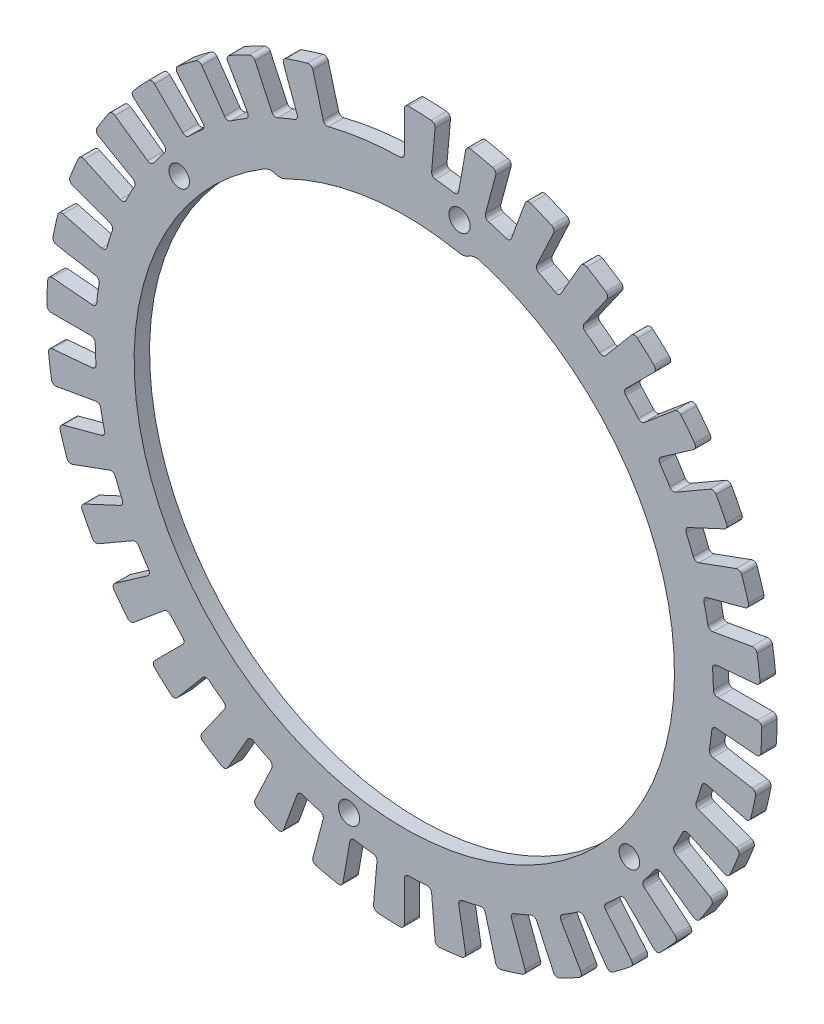
SolidWorks part; units mm, degrees
ref_plane "Front Plane" through (0, 0, 0) normal (0, 0, 1) x (1, 0, 0)
ref_plane "Top Plane" through (0, 0, 0) normal (0, 1, 0) x (1, 0, 0)
ref_plane "Right Plane" through (0, 0, 0) normal (1, 0, 0) x (0, 0, -1)
sketch "Sketch1" plane through (0, 0, 0) normal (0, 0, 1) x (1, 0, 0)
  line L0 (0, 82.7) -> (0, 71.5) construction
  line L1 (7.2078, 82.3853) -> (6.2316, 71.2279) construction
  line L2 (0, 71.5) -> (0, 0) construction
  line L3 (6.2316, 71.2279) -> (0, 0) construction
  line L4 (12.5883, 71.3918) -> (14.186, 80.4528) construction
  line L5 (12.5883, 71.3918) -> (0, 0) construction
  line L8 (0, 0) -> (12.7842, 65.769) construction
  line L12 (13.6428, 70.1863) -> (12.7842, 65.769) construction
  line L15 (12.7842, 65.769) -> (11.9256, 61.3517) construction
  line L18 (7.3144, 72.1301) -> (6.3182, 72.2172) construction
  line L21 (7.3144, 72.1301) -> (7.2135, 71.1352) construction
  line L24 (12.5883, 71.3918) -> (11.6035, 71.5654) construction
  line L27 (11.6035, 71.5654) -> (11.4434, 70.5783) construction
  line L30 (1.0122, 82.6938) -> (1, 81.6939) construction
  line L33 (1, 81.6939) -> (0, 81.6939) construction
  line L36 (7.1201, 81.383) -> (6.1239, 81.4702) construction
  line L39 (6.1239, 81.4702) -> (6.1989, 82.4674) construction
  line L42 (7.1201, 81.383) -> (6.3182, 72.2172)
  line L45 (0, 81.6939) -> (0, 72.4931)
  line L48 (0, 72.4931) -> (-1, 72.4931) construction
  line L51 (-1, 72.4931) -> (-0.9862, 71.4932) construction
  line L109 (0, -82.7) -> (0, -71.5) [skipped]
  line L111 (14.3607, 81.4436) -> (12.4158, 70.4138) [skipped]
  line L115 (41.35, 71.6203) -> (35.75, 61.9208) [skipped]
  line L117 (53.1585, 63.3519) -> (45.9593, 54.7722) [skipped]
  line L118 (-63.3519, -53.1585) -> (-54.7722, -45.9593) [skipped]
  line L119 (63.3519, 53.1585) -> (54.7722, 45.9593) [skipped]
  line L121 (71.6203, 41.35) -> (61.9208, 35.75) [skipped]
  line L123 (77.7126, 28.2851) -> (67.188, 24.4544) [skipped]
  line L125 (81.4436, 14.3607) -> (70.4138, 12.4158) [skipped]
  line L127 (82.7, 0) -> (71.5, 0) [skipped]
  line L129 (81.4436, -14.3607) -> (70.4138, -12.4158) [skipped]
  line L131 (77.7126, -28.2851) -> (67.188, -24.4544) [skipped]
  line L133 (71.6203, -41.35) -> (61.9208, -35.75) [skipped]
  line L135 (63.3519, -53.1585) -> (54.7722, -45.9593) [skipped]
  line L137 (53.1585, -63.3519) -> (45.9593, -54.7722) [skipped]
  line L139 (41.35, -71.6203) -> (35.75, -61.9208) [skipped]
  line L141 (28.2851, -77.7126) -> (24.4544, -67.188) [skipped]
  line L142 (14.3607, -81.4436) -> (12.4158, -70.4138) [skipped]
  line L143 (34.9505, 74.9517) -> (30.2172, 64.801) [skipped]
  line L144 (47.4348, 67.7439) -> (41.0107, 58.5694) [skipped]
  line L145 (58.4777, 58.4777) -> (50.5581, 50.5581) [skipped]
  line L146 (67.7439, 47.4348) -> (58.5694, 41.0107) [skipped]
  line L147 (74.9517, 34.9505) -> (64.801, 30.2172) [skipped]
  line L148 (79.8821, 21.4043) -> (69.0637, 18.5056) [skipped]
  line L149 (82.3853, 7.2078) -> (71.2279, 6.2316) [skipped]
  line L150 (82.3853, -7.2078) -> (71.2279, -6.2316) [skipped]
  line L151 (79.8821, -21.4043) -> (69.0637, -18.5056) [skipped]
  line L152 (74.9517, -34.9505) -> (64.801, -30.2172) [skipped]
  line L153 (67.7439, -47.4348) -> (58.5694, -41.0107) [skipped]
  line L154 (58.4777, -58.4777) -> (50.5581, -50.5581) [skipped]
  line L155 (47.4348, -67.7439) -> (41.0107, -58.5694) [skipped]
  line L156 (34.9505, -74.9517) -> (30.2172, -64.801) [skipped]
  line L157 (21.4043, -79.8821) -> (18.5056, -69.0637) [skipped]
  line L158 (7.2078, -82.3853) -> (6.2316, -71.2279) [skipped]
  line L159 (-7.2078, -82.3853) -> (-6.2316, -71.2279) [skipped]
  line L160 (-21.4043, -79.8821) -> (-18.5056, -69.0637) [skipped]
  line L161 (-34.9505, -74.9517) -> (-30.2172, -64.801) [skipped]
  line L162 (-47.4348, -67.7439) -> (-41.0107, -58.5694) [skipped]
  line L163 (-58.4777, -58.4777) -> (-50.5581, -50.5581) [skipped]
  line L164 (-67.7439, -47.4348) -> (-58.5694, -41.0107) [skipped]
  line L165 (-74.9517, -34.9505) -> (-64.801, -30.2172) [skipped]
  line L166 (-79.8821, -21.4043) -> (-69.0637, -18.5056) [skipped]
  line L167 (-82.3853, -7.2078) -> (-71.2279, -6.2316) [skipped]
  line L168 (-82.3853, 7.2078) -> (-71.2279, 6.2316) [skipped]
  line L169 (-79.8821, 21.4043) -> (-69.0637, 18.5056) [skipped]
  line L170 (-74.9517, 34.9505) -> (-64.801, 30.2172) [skipped]
  line L171 (-67.7439, 47.4348) -> (-58.5694, 41.0107) [skipped]
  line L172 (-58.4777, 58.4777) -> (-50.5581, 50.5581) [skipped]
  line L173 (-47.4348, 67.7439) -> (-41.0107, 58.5694) [skipped]
  line L174 (-34.9505, 74.9517) -> (-30.2172, 64.801) [skipped]
  line L175 (-21.4043, 79.8821) -> (-18.5056, 69.0637) [skipped]
  line L176 (21.4043, 79.8821) -> (18.5056, 69.0637) [skipped]
  line L209 (0, 0) -> (-12.7842, -65.769) construction
  line L210 (0, 0) -> (-52.0688, 42.1645) construction
  line L211 (0, 0) -> (52.0688, -42.1645) construction
  line L212 (14.186, 80.4528) -> (12.5883, 71.3918)
  line L213 (21.1439, 78.9102) -> (18.7626, 70.023)
  line L214 (27.941, 76.7671) -> (24.7941, 68.1212)
  line L215 (34.5253, 74.0398) -> (30.6369, 65.7011)
  line L216 (40.8469, 70.749) -> (36.2466, 62.7809)
  line L217 (46.8577, 66.9197) -> (41.5803, 59.3829)
  line L218 (52.5118, 62.5811) -> (46.5977, 55.5329)
  line L219 (57.7663, 57.7663) -> (51.2604, 51.2604)
  line L220 (62.5811, 52.5118) -> (55.5329, 46.5977)
  line L221 (66.9197, 46.8577) -> (59.3829, 41.5803)
  line L222 (70.749, 40.8469) -> (62.7809, 36.2466)
  line L223 (74.0398, 34.5253) -> (65.7011, 30.6369)
  line L224 (76.7671, 27.941) -> (68.1212, 24.7941)
  line L225 (78.9102, 21.1439) -> (70.023, 18.7626)
  line L226 (80.4528, 14.186) -> (71.3918, 12.5883)
  line L227 (81.383, 7.1201) -> (72.2172, 6.3182)
  line L228 (81.6939, 0) -> (72.4931, 0)
  line L229 (81.383, -7.1201) -> (72.2172, -6.3182)
  line L230 (80.4528, -14.186) -> (71.3918, -12.5883)
  line L231 (78.9102, -21.1439) -> (70.023, -18.7626)
  line L232 (76.7671, -27.941) -> (68.1212, -24.7941)
  line L233 (74.0398, -34.5253) -> (65.7011, -30.6369)
  line L234 (70.749, -40.8469) -> (62.7809, -36.2466)
  line L235 (66.9197, -46.8577) -> (59.3829, -41.5803)
  line L236 (62.5811, -52.5118) -> (55.5329, -46.5977)
  line L237 (57.7663, -57.7663) -> (51.2604, -51.2604)
  line L238 (52.5118, -62.5811) -> (46.5977, -55.5329)
  line L239 (46.8577, -66.9197) -> (41.5803, -59.3829)
  line L240 (40.8469, -70.749) -> (36.2466, -62.7809)
  line L241 (34.5253, -74.0398) -> (30.6369, -65.7011)
  line L242 (27.941, -76.7671) -> (24.7941, -68.1212)
  line L243 (21.1439, -78.9102) -> (18.7626, -70.023)
  line L244 (14.186, -80.4528) -> (12.5883, -71.3918)
  line L245 (7.1201, -81.383) -> (6.3182, -72.2172)
  line L246 (0, -81.6939) -> (0, -72.4931)
  line L247 (-7.1201, -81.383) -> (-6.3182, -72.2172)
  line L248 (-14.186, -80.4528) -> (-12.5883, -71.3918)
  line L249 (-21.1439, -78.9102) -> (-18.7626, -70.023)
  line L250 (-27.941, -76.7671) -> (-24.7941, -68.1212)
  line L251 (-34.5253, -74.0398) -> (-30.6369, -65.7011)
  line L252 (-40.8469, -70.749) -> (-36.2466, -62.7809)
  line L253 (-46.8577, -66.9197) -> (-41.5803, -59.3829)
  line L254 (-52.5118, -62.5811) -> (-46.5977, -55.5329)
  line L255 (-57.7663, -57.7663) -> (-51.2604, -51.2604)
  line L256 (-62.5811, -52.5118) -> (-55.5329, -46.5977)
  line L257 (-66.9197, -46.8577) -> (-59.3829, -41.5803)
  line L258 (-70.749, -40.8469) -> (-62.7809, -36.2466)
  line L259 (-74.0398, -34.5253) -> (-65.7011, -30.6369)
  line L260 (-76.7671, -27.941) -> (-68.1212, -24.7941)
  line L261 (-78.9102, -21.1439) -> (-70.023, -18.7626)
  line L262 (-80.4528, -14.186) -> (-71.3918, -12.5883)
  line L263 (-81.383, -7.1201) -> (-72.2172, -6.3182)
  line L264 (-81.6939, 0) -> (-72.4931, 0)
  line L265 (-81.383, 7.1201) -> (-72.2172, 6.3182)
  line L266 (-80.4528, 14.186) -> (-71.3918, 12.5883)
  line L267 (-78.9102, 21.1439) -> (-70.023, 18.7626)
  line L268 (-76.7671, 27.941) -> (-68.1212, 24.7941)
  line L269 (-74.0398, 34.5253) -> (-65.7011, 30.6369)
  line L270 (-70.749, 40.8469) -> (-62.7809, 36.2466)
  line L271 (-66.9197, 46.8577) -> (-59.3829, 41.5803)
  line L272 (-62.5811, 52.5118) -> (-55.5329, 46.5977)
  line L273 (-57.7663, 57.7663) -> (-51.2604, 51.2604)
  line L274 (-52.5118, 62.5811) -> (-46.5977, 55.5329)
  line L275 (-46.8577, 66.9197) -> (-41.5803, 59.3829)
  line L276 (-40.8469, 70.749) -> (-36.2466, 62.7809)
  line L277 (-34.5253, 74.0398) -> (-30.6369, 65.7011)
  line L278 (-27.941, 76.7671) -> (-24.7941, 68.1212)
  line L279 (-21.1439, 78.9102) -> (-18.7626, 70.023)
  line L280 (-0.9864, 71.4932) -> (-0.9862, 71.4932)
  line L281 (-32.3995, 53.4464) -> (-30.8444, 50.881) construction
  line L282 (-30.8444, 50.881) -> (-29.8635, 53.7161) construction
  line L283 (-29.8635, 53.7161) -> (-28.8826, 56.5512) construction
  line L284 (-28.8826, 56.5512) -> (-27.5181, 53.8795) construction
  line L285 (17.4626, 60.0109) -> (16.6244, 57.1304) construction
  line L286 (16.6244, 57.1304) -> (14.9432, 59.615) construction
  line L289 (13.262, 62.0997) -> (14.9432, 59.615) construction
  line L290 (-7.4414, 56.5227) -> (0, 0) construction
  line L291 (-27.5181, 53.8795) -> (-7.4414, 56.5227) construction
  line L292 (-7.4414, 56.5227) -> (12.6354, 59.1658) construction
  line L293 (13.262, 62.0997) -> (12.6354, 59.1658) construction
  line L294 (-28.4278, 55.6607) -> (13.0531, 61.1217) construction
  circle A0 centre (0, 0) radius 82.7 construction
  arc A1 (-32.3995, 53.4464) -> (17.4626, 60.0109) centre (0, 0) ccw
  circle A73 centre (12.7842, 65.769) radius 2.4585
  circle A74 centre (12.7842, 65.769) radius 2.987 construction
  arc A78 (0, 71.5) -> (6.2316, 71.2279) centre (0, 0) cw construction
  arc A79 (6.3182, 72.2172) -> (7.2135, 71.1352) centre (7.3144, 72.1301) ccw
  arc A80 (11.4434, 70.5783) -> (12.5883, 71.3918) centre (11.6035, 71.5654) ccw construction
  arc A81 (7.1201, 81.383) -> (6.1989, 82.4674) centre (6.1239, 81.4702) ccw
  arc A82 (0, 81.6939) -> (1.0122, 82.6938) centre (1, 81.6939) cw
  arc A83 (6.5367, 74.7146) -> (13.0236, 73.8606) centre (0, 0) cw [skipped]
  arc A84 (7.2135, 71.1352) -> (11.4434, 70.5783) centre (0, 0) cw
  arc A85 (0, 82.7) -> (7.2078, 82.3853) centre (0, 0) cw [skipped]
  arc A86 (1.0122, 82.6938) -> (6.1989, 82.4674) centre (0, 0) cw
  arc A87 (28.2851, 77.7126) -> (34.9505, 74.9517) centre (0, 0) cw [skipped]
  arc A88 (31.6964, 67.9731) -> (37.5, 64.9519) centre (0, 0) cw [skipped]
  arc A89 (41.35, 71.6203) -> (47.4348, 67.7439) centre (0, 0) cw [skipped]
  arc A90 (43.0182, 61.4364) -> (48.2091, 57.4533) centre (0, 0) cw [skipped]
  arc A91 (53.1585, 63.3519) -> (58.4777, 58.4777) centre (0, 0) cw [skipped]
  arc A92 (53.033, 53.033) -> (57.4533, 48.2091) centre (0, 0) cw [skipped]
  arc A93 (63.3519, 53.1585) -> (67.7439, 47.4348) centre (0, 0) cw [skipped]
  arc A94 (61.4364, 43.0182) -> (64.9519, 37.5) centre (0, 0) cw [skipped]
  arc A95 (71.6203, 41.35) -> (74.9517, 34.9505) centre (0, 0) cw [skipped]
  arc A96 (67.9731, 31.6964) -> (70.4769, 25.6515) centre (0, 0) cw [skipped]
  arc A97 (77.7126, 28.2851) -> (79.8821, 21.4043) centre (0, 0) cw [skipped]
  arc A98 (72.4444, 19.4114) -> (73.8606, 13.0236) centre (0, 0) cw [skipped]
  arc A99 (81.4436, 14.3607) -> (82.3853, 7.2078) centre (0, 0) cw [skipped]
  arc A100 (74.7146, 6.5367) -> (75, 0) centre (0, 0) cw [skipped]
  arc A101 (82.7, 0) -> (82.3853, -7.2078) centre (0, 0) cw [skipped]
  arc A102 (74.7146, -6.5367) -> (73.8606, -13.0236) centre (0, 0) cw [skipped]
  arc A103 (81.4436, -14.3607) -> (79.8821, -21.4043) centre (0, 0) cw [skipped]
  arc A104 (72.4444, -19.4114) -> (70.4769, -25.6515) centre (0, 0) cw [skipped]
  arc A105 (77.7126, -28.2851) -> (74.9517, -34.9505) centre (0, 0) cw [skipped]
  arc A106 (67.9731, -31.6964) -> (64.9519, -37.5) centre (0, 0) cw [skipped]
  arc A107 (71.6203, -41.35) -> (67.7439, -47.4348) centre (0, 0) cw [skipped]
  arc A108 (61.4364, -43.0182) -> (57.4533, -48.2091) centre (0, 0) cw [skipped]
  arc A109 (63.3519, -53.1585) -> (58.4777, -58.4777) centre (0, 0) cw [skipped]
  arc A110 (53.033, -53.033) -> (48.2091, -57.4533) centre (0, 0) cw [skipped]
  arc A111 (53.1585, -63.3519) -> (47.4348, -67.7439) centre (0, 0) cw [skipped]
  arc A112 (43.0182, -61.4364) -> (37.5, -64.9519) centre (0, 0) cw [skipped]
  arc A113 (41.35, -71.6203) -> (34.9505, -74.9517) centre (0, 0) cw [skipped]
  arc A114 (31.6964, -67.9731) -> (25.6515, -70.4769) centre (0, 0) cw [skipped]
  arc A115 (28.2851, -77.7126) -> (21.4043, -79.8821) centre (0, 0) cw [skipped]
  arc A116 (19.4114, -72.4444) -> (13.0236, -73.8606) centre (0, 0) cw [skipped]
  arc A117 (14.3607, -81.4436) -> (7.2078, -82.3853) centre (0, 0) cw [skipped]
  arc A118 (6.5367, -74.7146) -> (0, -75) centre (0, 0) cw [skipped]
  arc A119 (0, -82.7) -> (-7.2078, -82.3853) centre (0, 0) cw [skipped]
  arc A120 (-6.5367, -74.7146) -> (-13.0236, -73.8606) centre (0, 0) cw [skipped]
  arc A121 (-14.3607, -81.4436) -> (-21.4043, -79.8821) centre (0, 0) cw [skipped]
  arc A122 (-28.2851, -77.7126) -> (-34.9505, -74.9517) centre (0, 0) cw [skipped]
  arc A123 (-19.4114, -72.4444) -> (-25.6515, -70.4769) centre (0, 0) cw [skipped]
  arc A124 (-31.6964, -67.9731) -> (-37.5, -64.9519) centre (0, 0) cw [skipped]
  arc A125 (-41.35, -71.6203) -> (-47.4348, -67.7439) centre (0, 0) cw [skipped]
  arc A126 (-43.0182, -61.4364) -> (-48.2091, -57.4533) centre (0, 0) cw [skipped]
  arc A127 (-53.1585, -63.3519) -> (-58.4777, -58.4777) centre (0, 0) cw [skipped]
  arc A128 (-53.033, -53.033) -> (-57.4533, -48.2091) centre (0, 0) cw [skipped]
  arc A129 (-63.3519, -53.1585) -> (-67.7439, -47.4348) centre (0, 0) cw [skipped]
  arc A130 (-61.4364, -43.0182) -> (-64.9519, -37.5) centre (0, 0) cw [skipped]
  arc A131 (-71.6203, -41.35) -> (-74.9517, -34.9505) centre (0, 0) cw [skipped]
  arc A132 (-67.9731, -31.6964) -> (-70.4769, -25.6515) centre (0, 0) cw [skipped]
  arc A133 (-77.7126, -28.2851) -> (-79.8821, -21.4043) centre (0, 0) cw [skipped]
  arc A134 (-72.4444, -19.4114) -> (-73.8606, -13.0236) centre (0, 0) cw [skipped]
  arc A135 (-81.4436, -14.3607) -> (-82.3853, -7.2078) centre (0, 0) cw [skipped]
  arc A136 (-74.7146, -6.5367) -> (-75, 0) centre (0, 0) cw [skipped]
  arc A137 (-82.7, 0) -> (-82.3853, 7.2078) centre (0, 0) cw [skipped]
  arc A138 (-74.7146, 6.5367) -> (-73.8606, 13.0236) centre (0, 0) cw [skipped]
  arc A139 (-81.4436, 14.3607) -> (-79.8821, 21.4043) centre (0, 0) cw [skipped]
  arc A140 (-72.4444, 19.4114) -> (-70.4769, 25.6515) centre (0, 0) cw [skipped]
  arc A141 (-77.7126, 28.2851) -> (-74.9517, 34.9505) centre (0, 0) cw [skipped]
  arc A142 (-67.9731, 31.6964) -> (-64.9519, 37.5) centre (0, 0) cw [skipped]
  arc A143 (-71.6203, 41.35) -> (-67.7439, 47.4348) centre (0, 0) cw [skipped]
  arc A144 (-61.4364, 43.0182) -> (-57.4533, 48.2091) centre (0, 0) cw [skipped]
  arc A145 (-63.3519, 53.1585) -> (-58.4777, 58.4777) centre (0, 0) cw [skipped]
  arc A146 (-53.033, 53.033) -> (-48.2091, 57.4533) centre (0, 0) cw [skipped]
  arc A147 (-53.1585, 63.3519) -> (-47.4348, 67.7439) centre (0, 0) cw [skipped]
  arc A148 (-43.0182, 61.4364) -> (-37.5, 64.9519) centre (0, 0) cw [skipped]
  arc A149 (-41.35, 71.6203) -> (-34.9505, 74.9517) centre (0, 0) cw [skipped]
  arc A150 (-31.6964, 67.9731) -> (-25.6515, 70.4769) centre (0, 0) cw [skipped]
  arc A151 (-28.2851, 77.7126) -> (-21.4043, 79.8821) centre (0, 0) cw [skipped]
  arc A152 (-19.4114, 72.4444) -> (-13.0236, 73.8606) centre (0, 0) cw [skipped]
  arc A153 (14.3607, 81.4436) -> (21.4043, 79.8821) centre (0, 0) cw [skipped]
  arc A154 (19.4114, 72.4444) -> (25.6515, 70.4769) centre (0, 0) cw [skipped]
  arc A155 (0, 72.4931) -> (-0.9862, 71.4932) centre (-1, 72.4931) cw
  circle A367 centre (-12.7842, -65.769) radius 2.4585
  circle A368 centre (52.0688, -42.1645) radius 2.3812
  circle A369 centre (-52.0688, 42.1645) radius 2.3813
  circle A370 centre (0, 0) radius 71.5 construction
  arc A371 (12.5883, 71.3918) -> (11.4434, 70.5783) centre (11.6035, 71.5654) cw
  arc A372 (14.186, 80.4528) -> (15.3565, 81.2617) centre (15.1708, 80.2791) cw
  arc A373 (15.3565, 81.2617) -> (20.425, 80.1381) centre (0, 0) cw
  arc A374 (21.1439, 78.9102) -> (20.425, 80.1381) centre (20.178, 79.169) ccw
  arc A375 (18.7626, 70.023) -> (19.4564, 68.8019) centre (19.7285, 69.7641) ccw
  arc A376 (19.4564, 68.8019) -> (23.5254, 67.5189) centre (0, 0) cw
  arc A377 (24.7941, 68.1212) -> (23.5254, 67.5189) centre (23.8544, 68.4633) cw
  arc A378 (27.941, 76.7671) -> (29.2341, 77.3606) centre (28.8806, 76.4251) cw
  arc A379 (29.2341, 77.3606) -> (34.0305, 75.3738) centre (0, 0) cw
  arc A380 (34.5253, 74.0398) -> (34.0305, 75.3738) centre (33.619, 74.4624) ccw
  arc A381 (30.6369, 65.7011) -> (31.1081, 64.3781) centre (31.5432, 65.2784) ccw
  arc A382 (31.1081, 64.3781) -> (34.8925, 62.408) centre (0, 0) cw
  arc A384 (36.2466, 62.7809) -> (34.8925, 62.408) centre (35.3805, 63.2809) cw
  arc A385 (40.8469, 70.749) -> (42.2235, 71.1088) centre (41.713, 70.249) cw
  arc A386 (42.2235, 71.1088) -> (46.602, 68.3194) centre (0, 0) cw
  arc A387 (46.8577, 66.9197) -> (46.602, 68.3194) centre (46.0385, 67.4933) ccw
  arc A388 (41.5803, 59.3829) -> (41.8147, 57.9981) centre (42.3995, 58.8093) ccw
  arc A389 (41.8147, 57.9981) -> (45.1995, 55.4009) centre (0, 0) cw
  arc A390 (46.5977, 55.5329) -> (45.1995, 55.4009) centre (45.8316, 56.1757) cw
  arc A391 (52.5118, 62.5811) -> (53.93, 62.6965) centre (53.2779, 61.9384) cw
  arc A392 (53.93, 62.6965) -> (57.7576, 59.1891) centre (0, 0) cw
  arc A393 (57.7663, 57.7663) -> (57.7576, 59.1891) centre (57.0592, 58.4734) ccw
  arc A394 (51.2604, 51.2604) -> (51.2507, 49.856) centre (51.9675, 50.5533) ccw
  arc A395 (51.2507, 49.856) -> (54.133, 46.7104) centre (0, 0) cw
  arc A396 (55.5329, 46.5977) -> (54.133, 46.7104) centre (54.8902, 47.3637) cw
  arc A397 (62.5811, 52.5118) -> (63.9978, 52.3791) centre (63.2239, 51.7458) cw
  arc A398 (63.9978, 52.3791) -> (67.1582, 48.2604) centre (0, 0) cw
  arc A399 (66.9197, 46.8577) -> (67.1582, 48.2604) centre (66.3461, 47.6768) ccw
  arc A400 (59.3829, 41.5803) -> (59.1295, 40.199) centre (59.9565, 40.7612) ccw
  arc A401 (59.1295, 40.199) -> (61.4218, 36.6007) centre (0, 0) cw
  arc A402 (62.7809, 36.2466) -> (61.4218, 36.6007) centre (62.2809, 37.1126) cw
  arc A403 (70.749, 40.8469) -> (72.1211, 40.4703) centre (71.249, 39.9809) cw
  arc A404 (72.1211, 40.4703) -> (74.5182, 35.8653) centre (0, 0) cw
  arc A405 (74.0398, 34.5253) -> (74.5182, 35.8653) centre (73.6172, 35.4316) ccw
  arc A406 (65.7011, 30.6369) -> (65.2116, 29.3205) centre (66.1237, 29.7306) ccw
  arc A407 (65.2116, 29.3205) -> (66.8443, 25.3788) centre (0, 0) cw
  arc A408 (68.1212, 24.7941) -> (66.8443, 25.3788) centre (67.7792, 25.7338) cw
  arc A409 (76.7671, 27.941) -> (78.053, 27.3318) centre (77.1092, 27.0013) cw
  arc A410 (78.053, 27.3318) -> (79.6141, 22.3805) centre (0, 0) cw
  arc A411 (78.9102, 21.1439) -> (79.6141, 22.3805) centre (78.6514, 22.1099) ccw
  arc A412 (70.023, 18.7626) -> (69.3124, 17.5512) centre (70.2818, 17.7967) ccw
  arc A413 (69.3124, 17.5512) -> (70.2358, 13.3859) centre (0, 0) cw
  arc A414 (71.3918, 12.5883) -> (70.2358, 13.3859) centre (71.2181, 13.5731) cw
  arc A415 (80.4528, 14.186) -> (81.6133, 13.3628) centre (80.6264, 13.2012) cw
  arc A416 (81.6133, 13.3628) -> (82.2909, 8.2156) centre (0, 0) cw
  arc A417 (81.383, 7.1201) -> (82.2909, 8.2156) centre (81.2959, 8.1163) ccw
  arc A418 (72.2172, 6.3182) -> (71.3071, 5.2486) centre (72.3044, 5.322) ccw
  arc A419 (71.3071, 5.2486) -> (71.4932, 0.9862) centre (0, 0) cw
  arc A420 (72.4931, 0) -> (71.4932, 0.9862) centre (72.4931, 1) cw
  arc A421 (81.6939, 0) -> (82.6938, -1.0122) centre (81.6939, -1) cw
  arc A422 (82.6938, -1.0122) -> (82.4674, -6.1989) centre (0, 0) cw
  arc A423 (81.383, -7.1201) -> (82.4674, -6.1989) centre (81.4702, -6.1239) ccw
  arc A424 (72.2172, -6.3182) -> (71.1352, -7.2135) centre (72.1301, -7.3144) ccw
  arc A425 (71.1352, -7.2135) -> (70.5783, -11.4434) centre (0, 0) cw
  arc A426 (71.3918, -12.5883) -> (70.5783, -11.4434) centre (71.5654, -11.6035) cw
  arc A427 (80.4528, -14.186) -> (81.2617, -15.3565) centre (80.2791, -15.1708) cw
  arc A428 (81.2617, -15.3565) -> (80.1381, -20.425) centre (0, 0) cw
  arc A429 (78.9102, -21.1439) -> (80.1381, -20.425) centre (79.169, -20.178) ccw
  arc A430 (70.023, -18.7626) -> (68.8019, -19.4564) centre (69.7641, -19.7285) ccw
  arc A431 (68.8019, -19.4564) -> (67.5189, -23.5254) centre (0, 0) cw
  arc A432 (68.1212, -24.7941) -> (67.5189, -23.5254) centre (68.4633, -23.8544) cw
  arc A433 (76.7671, -27.941) -> (77.3606, -29.2341) centre (76.4251, -28.8806) cw
  arc A434 (77.3606, -29.2341) -> (75.3738, -34.0305) centre (0, 0) cw
  arc A435 (74.0398, -34.5253) -> (75.3738, -34.0305) centre (74.4624, -33.619) ccw
  arc A436 (65.7011, -30.6369) -> (64.3781, -31.1081) centre (65.2784, -31.5432) ccw
  arc A437 (64.3781, -31.1081) -> (62.408, -34.8925) centre (0, 0) cw
  arc A438 (62.7809, -36.2466) -> (62.408, -34.8925) centre (63.2809, -35.3805) cw
  arc A439 (70.749, -40.8469) -> (71.1088, -42.2235) centre (70.249, -41.713) cw
  arc A440 (71.1088, -42.2235) -> (68.3194, -46.602) centre (0, 0) cw
  arc A441 (66.9197, -46.8577) -> (68.3194, -46.602) centre (67.4933, -46.0385) ccw
  arc A442 (59.3829, -41.5803) -> (57.9981, -41.8147) centre (58.8093, -42.3995) ccw
  arc A443 (57.9981, -41.8147) -> (55.4009, -45.1995) centre (0, 0) cw
  arc A444 (55.5329, -46.5977) -> (55.4009, -45.1995) centre (56.1757, -45.8316) cw
  arc A445 (62.5811, -52.5118) -> (62.6965, -53.93) centre (61.9384, -53.2779) cw
  arc A446 (62.6965, -53.93) -> (59.1891, -57.7576) centre (0, 0) cw
  arc A447 (57.7663, -57.7663) -> (59.1891, -57.7576) centre (58.4734, -57.0592) ccw
  arc A448 (51.2604, -51.2604) -> (49.856, -51.2507) centre (50.5533, -51.9675) ccw
  arc A449 (49.856, -51.2507) -> (46.7104, -54.133) centre (0, 0) cw
  arc A450 (46.5977, -55.5329) -> (46.7104, -54.133) centre (47.3637, -54.8902) cw
  arc A451 (52.5118, -62.5811) -> (52.3791, -63.9978) centre (51.7458, -63.2239) cw
  arc A452 (52.3791, -63.9978) -> (48.2604, -67.1582) centre (0, 0) cw
  arc A453 (46.8577, -66.9197) -> (48.2604, -67.1582) centre (47.6768, -66.3461) ccw
  arc A454 (41.5803, -59.3829) -> (40.199, -59.1295) centre (40.7612, -59.9565) ccw
  arc A455 (40.199, -59.1295) -> (36.6007, -61.4218) centre (0, 0) cw
  arc A456 (36.2466, -62.7809) -> (36.6007, -61.4218) centre (37.1126, -62.2809) cw
  arc A457 (40.8469, -70.749) -> (40.4703, -72.1211) centre (39.9809, -71.249) cw
  arc A458 (40.4703, -72.1211) -> (35.8653, -74.5182) centre (0, 0) cw
  arc A459 (34.5253, -74.0398) -> (35.8653, -74.5182) centre (35.4316, -73.6172) ccw
  arc A460 (30.6369, -65.7011) -> (29.3205, -65.2116) centre (29.7306, -66.1237) ccw
  arc A461 (29.3205, -65.2116) -> (25.3788, -66.8443) centre (0, 0) cw
  arc A462 (24.7941, -68.1212) -> (25.3788, -66.8443) centre (25.7338, -67.7792) cw
  arc A463 (27.941, -76.7671) -> (27.3318, -78.053) centre (27.0013, -77.1092) cw
  arc A464 (27.3318, -78.053) -> (22.3805, -79.6141) centre (0, 0) cw
  arc A465 (21.1439, -78.9102) -> (22.3805, -79.6141) centre (22.1099, -78.6514) ccw
  arc A466 (18.7626, -70.023) -> (17.5512, -69.3124) centre (17.7967, -70.2818) ccw
  arc A467 (17.5512, -69.3124) -> (13.3859, -70.2358) centre (0, 0) cw
  arc A468 (12.5883, -71.3918) -> (13.3859, -70.2358) centre (13.5731, -71.2181) cw
  arc A469 (14.186, -80.4528) -> (13.3628, -81.6133) centre (13.2012, -80.6264) cw
  arc A470 (13.3628, -81.6133) -> (8.2156, -82.2909) centre (0, 0) cw
  arc A471 (7.1201, -81.383) -> (8.2156, -82.2909) centre (8.1163, -81.2959) ccw
  arc A472 (6.3182, -72.2172) -> (5.2486, -71.3071) centre (5.322, -72.3044) ccw
  arc A473 (5.2486, -71.3071) -> (0.9862, -71.4932) centre (0, 0) cw
  arc A474 (0, -72.4931) -> (0.9862, -71.4932) centre (1, -72.4931) cw
  arc A475 (0, -81.6939) -> (-1.0122, -82.6938) centre (-1, -81.6939) cw
  arc A476 (-1.0122, -82.6938) -> (-6.1989, -82.4674) centre (0, 0) cw
  arc A477 (-7.1201, -81.383) -> (-6.1989, -82.4674) centre (-6.1239, -81.4702) ccw
  arc A478 (-6.3182, -72.2172) -> (-7.2135, -71.1352) centre (-7.3144, -72.1301) ccw
  arc A479 (-7.2135, -71.1352) -> (-11.4434, -70.5783) centre (0, 0) cw
  arc A480 (-12.5883, -71.3918) -> (-11.4434, -70.5783) centre (-11.6035, -71.5654) cw
  arc A481 (-14.186, -80.4528) -> (-15.3565, -81.2617) centre (-15.1708, -80.2791) cw
  arc A482 (-15.3565, -81.2617) -> (-20.425, -80.1381) centre (0, 0) cw
  arc A483 (-21.1439, -78.9102) -> (-20.425, -80.1381) centre (-20.178, -79.169) ccw
  arc A484 (-18.7626, -70.023) -> (-19.4564, -68.8019) centre (-19.7285, -69.7641) ccw
  arc A485 (-19.4564, -68.8019) -> (-23.5254, -67.5189) centre (0, 0) cw
  arc A486 (-24.7941, -68.1212) -> (-23.5254, -67.5189) centre (-23.8544, -68.4633) cw
  arc A487 (-27.941, -76.7671) -> (-29.2341, -77.3606) centre (-28.8806, -76.4251) cw
  arc A488 (-29.2341, -77.3606) -> (-34.0305, -75.3738) centre (0, 0) cw
  arc A489 (-34.5253, -74.0398) -> (-34.0305, -75.3738) centre (-33.619, -74.4624) ccw
  arc A490 (-30.6369, -65.7011) -> (-31.1081, -64.3781) centre (-31.5432, -65.2784) ccw
  arc A491 (-31.1081, -64.3781) -> (-34.8925, -62.408) centre (0, 0) cw
  arc A492 (-36.2466, -62.7809) -> (-34.8925, -62.408) centre (-35.3805, -63.2809) cw
  arc A493 (-40.8469, -70.749) -> (-42.2235, -71.1088) centre (-41.713, -70.249) cw
  arc A494 (-42.2235, -71.1088) -> (-46.602, -68.3194) centre (0, 0) cw
  arc A495 (-46.8577, -66.9197) -> (-46.602, -68.3194) centre (-46.0385, -67.4933) ccw
  arc A496 (-41.5803, -59.3829) -> (-41.8147, -57.9981) centre (-42.3995, -58.8093) ccw
  arc A497 (-41.8147, -57.9981) -> (-45.1995, -55.4009) centre (0, 0) cw
  arc A498 (-46.5977, -55.5329) -> (-45.1995, -55.4009) centre (-45.8316, -56.1757) cw
  arc A499 (-52.5118, -62.5811) -> (-53.93, -62.6965) centre (-53.2779, -61.9384) cw
  arc A500 (-53.93, -62.6965) -> (-57.7576, -59.1891) centre (0, 0) cw
  arc A501 (-57.7663, -57.7663) -> (-57.7576, -59.1891) centre (-57.0592, -58.4734) ccw
  arc A502 (-51.2604, -51.2604) -> (-51.2507, -49.856) centre (-51.9675, -50.5533) ccw
  arc A503 (-51.2507, -49.856) -> (-54.133, -46.7104) centre (0, 0) cw
  arc A504 (-55.5329, -46.5977) -> (-54.133, -46.7104) centre (-54.8902, -47.3637) cw
  arc A505 (-62.5811, -52.5118) -> (-63.9978, -52.3791) centre (-63.2239, -51.7458) cw
  arc A506 (-63.9978, -52.3791) -> (-67.1582, -48.2604) centre (0, 0) cw
  arc A507 (-66.9197, -46.8577) -> (-67.1582, -48.2604) centre (-66.3461, -47.6768) ccw
  arc A508 (-59.3829, -41.5803) -> (-59.1295, -40.199) centre (-59.9565, -40.7612) ccw
  arc A509 (-59.1295, -40.199) -> (-61.4218, -36.6007) centre (0, 0) cw
  arc A510 (-62.7809, -36.2466) -> (-61.4218, -36.6007) centre (-62.2809, -37.1126) cw
  arc A511 (-70.749, -40.8469) -> (-72.1211, -40.4703) centre (-71.249, -39.9809) cw
  arc A512 (-72.1211, -40.4703) -> (-74.5182, -35.8653) centre (0, 0) cw
  arc A513 (-74.0398, -34.5253) -> (-74.5182, -35.8653) centre (-73.6172, -35.4316) ccw
  arc A514 (-65.7011, -30.6369) -> (-65.2116, -29.3205) centre (-66.1237, -29.7306) ccw
  arc A515 (-65.2116, -29.3205) -> (-66.8443, -25.3788) centre (0, 0) cw
  arc A516 (-68.1212, -24.7941) -> (-66.8443, -25.3788) centre (-67.7792, -25.7338) cw
  arc A517 (-76.7671, -27.941) -> (-78.053, -27.3318) centre (-77.1092, -27.0013) cw
  arc A518 (-78.053, -27.3318) -> (-79.6141, -22.3805) centre (0, 0) cw
  arc A519 (-78.9102, -21.1439) -> (-79.6141, -22.3805) centre (-78.6514, -22.1099) ccw
  arc A520 (-70.023, -18.7626) -> (-69.3124, -17.5512) centre (-70.2818, -17.7967) ccw
  arc A521 (-69.3124, -17.5512) -> (-70.2358, -13.3859) centre (0, 0) cw
  arc A522 (-71.3918, -12.5883) -> (-70.2358, -13.3859) centre (-71.2181, -13.5731) cw
  arc A523 (-80.4528, -14.186) -> (-81.6133, -13.3628) centre (-80.6264, -13.2012) cw
  arc A524 (-81.6133, -13.3628) -> (-82.2909, -8.2156) centre (0, 0) cw
  arc A525 (-81.383, -7.1201) -> (-82.2909, -8.2156) centre (-81.2959, -8.1163) ccw
  arc A526 (-72.2172, -6.3182) -> (-71.3071, -5.2486) centre (-72.3044, -5.322) ccw
  arc A527 (-71.3071, -5.2486) -> (-71.4932, -0.9862) centre (0, 0) cw
  arc A528 (-72.4931, 0) -> (-71.4932, -0.9862) centre (-72.4931, -1) cw
  arc A529 (-81.6939, 0) -> (-82.6938, 1.0122) centre (-81.6939, 1) cw
  arc A530 (-82.6938, 1.0122) -> (-82.4674, 6.1989) centre (0, 0) cw
  arc A531 (-81.383, 7.1201) -> (-82.4674, 6.1989) centre (-81.4702, 6.1239) ccw
  arc A532 (-72.2172, 6.3182) -> (-71.1352, 7.2135) centre (-72.1301, 7.3144) ccw
  arc A533 (-71.1352, 7.2135) -> (-70.5783, 11.4434) centre (0, 0) cw
  arc A534 (-71.3918, 12.5883) -> (-70.5783, 11.4434) centre (-71.5654, 11.6035) cw
  arc A535 (-80.4528, 14.186) -> (-81.2617, 15.3565) centre (-80.2791, 15.1708) cw
  arc A536 (-81.2617, 15.3565) -> (-80.1381, 20.425) centre (0, 0) cw
  arc A537 (-78.9102, 21.1439) -> (-80.1381, 20.425) centre (-79.169, 20.178) ccw
  arc A538 (-70.023, 18.7626) -> (-68.8019, 19.4564) centre (-69.7641, 19.7285) ccw
  arc A539 (-68.8019, 19.4564) -> (-67.5189, 23.5254) centre (0, 0) cw
  arc A540 (-68.1212, 24.7941) -> (-67.5189, 23.5254) centre (-68.4633, 23.8544) cw
  arc A541 (-76.7671, 27.941) -> (-77.3606, 29.2341) centre (-76.4251, 28.8806) cw
  arc A542 (-77.3606, 29.2341) -> (-75.3738, 34.0305) centre (0, 0) cw
  arc A543 (-74.0398, 34.5253) -> (-75.3738, 34.0305) centre (-74.4624, 33.619) ccw
  arc A544 (-65.7011, 30.6369) -> (-64.3781, 31.1081) centre (-65.2784, 31.5432) ccw
  arc A545 (-64.3781, 31.1081) -> (-62.408, 34.8925) centre (0, 0) cw
  arc A546 (-62.7809, 36.2466) -> (-62.408, 34.8925) centre (-63.2809, 35.3805) cw
  arc A547 (-70.749, 40.8469) -> (-71.1088, 42.2235) centre (-70.249, 41.713) cw
  arc A548 (-71.1088, 42.2235) -> (-68.3194, 46.602) centre (0, 0) cw
  arc A549 (-66.9197, 46.8577) -> (-68.3194, 46.602) centre (-67.4933, 46.0385) ccw
  arc A550 (-59.3829, 41.5803) -> (-57.9981, 41.8147) centre (-58.8093, 42.3995) ccw
  arc A551 (-57.9981, 41.8147) -> (-55.4009, 45.1995) centre (0, 0) cw
  arc A552 (-55.5329, 46.5977) -> (-55.4009, 45.1995) centre (-56.1757, 45.8316) cw
  arc A553 (-62.5811, 52.5118) -> (-62.6965, 53.93) centre (-61.9384, 53.2779) cw
  arc A554 (-62.6965, 53.93) -> (-59.1891, 57.7576) centre (0, 0) cw
  arc A555 (-57.7663, 57.7663) -> (-59.1891, 57.7576) centre (-58.4734, 57.0592) ccw
  arc A556 (-51.2604, 51.2604) -> (-49.856, 51.2507) centre (-50.5533, 51.9675) ccw
  arc A557 (-49.856, 51.2507) -> (-46.7104, 54.133) centre (0, 0) cw
  arc A558 (-46.5977, 55.5329) -> (-46.7104, 54.133) centre (-47.3637, 54.8902) cw
  arc A559 (-52.5118, 62.5811) -> (-52.3791, 63.9978) centre (-51.7458, 63.2239) cw
  arc A560 (-52.3791, 63.9978) -> (-48.2604, 67.1582) centre (0, 0) cw
  arc A561 (-46.8577, 66.9197) -> (-48.2604, 67.1582) centre (-47.6768, 66.3461) ccw
  arc A562 (-41.5803, 59.3829) -> (-40.199, 59.1295) centre (-40.7612, 59.9565) ccw
  arc A563 (-40.199, 59.1295) -> (-36.6007, 61.4218) centre (0, 0) cw
  arc A564 (-36.2466, 62.7809) -> (-36.6007, 61.4218) centre (-37.1126, 62.2809) cw
  arc A565 (-40.8469, 70.749) -> (-40.4703, 72.1211) centre (-39.9809, 71.249) cw
  arc A566 (-40.4703, 72.1211) -> (-35.8653, 74.5182) centre (0, 0) cw
  arc A567 (-34.5253, 74.0398) -> (-35.8653, 74.5182) centre (-35.4316, 73.6172) ccw
  arc A568 (-30.6369, 65.7011) -> (-29.3205, 65.2116) centre (-29.7306, 66.1237) ccw
  arc A569 (-29.3205, 65.2116) -> (-25.3788, 66.8443) centre (0, 0) cw
  arc A570 (-24.7941, 68.1212) -> (-25.3788, 66.8443) centre (-25.7338, 67.7792) cw
  arc A571 (-27.941, 76.7671) -> (-27.3318, 78.053) centre (-27.0013, 77.1092) cw
  arc A572 (-27.3318, 78.053) -> (-22.3805, 79.6141) centre (0, 0) cw
  arc A573 (-21.1439, 78.9102) -> (-22.3805, 79.6141) centre (-22.1099, 78.6514) ccw
  arc A574 (-18.7626, 70.023) -> (-17.5512, 69.3124) centre (-17.7967, 70.2818) ccw
  arc A575 (-17.5512, 69.3124) -> (-13.3859, 70.2358) centre (0, 0) cw
  arc A576 (-13.3859, 70.2358) -> (-0.9864, 71.4932) centre (0, 0) cw
  arc A577 (-29.8635, 53.7161) -> (-32.3995, 53.4464) centre (-30.8444, 50.881) ccw
  arc A578 (-29.8635, 53.7161) -> (-27.5181, 53.8795) centre (-28.8826, 56.5512) ccw
  arc A579 (17.4626, 60.0109) -> (14.9432, 59.615) centre (16.6244, 57.1304) ccw
  arc A580 (14.9432, 59.615) -> (12.6354, 59.1658) centre (13.262, 62.0997) cw
  circle A582 centre (0, 0) radius 62.5 construction
  arc A586 (-27.5181, 53.8795) -> (12.6354, 59.1658) centre (0.3099, -2.3542) cw
  point P3 (-28.4278, 55.6607)
  point P29 (0, 0)
  point P133 (13.0531, 61.1217)
  point P185 (0, 0)
  point P252 (0, 0)
  point P703 (0, 0)
  point P728 (0, 0)
  point P763 (0, 0)
  dimension "D2" = 165.4
  dimension "D7" = 4.917
  dimension "D8" = 5.974
  dimension "D12" = 1
  dimension "D14" = 11.2
  dimension "D15" = 11.2
  dimension "D17" = 2
  dimension "D20" = 4.7625
  dimension "D21" = 4.917
  dimension "D22" = 4.7625
  dimension "D3" = 5
  dimension "D4" = 67
  dimension "D6" = 11
  dimension "D10" = 62
  dimension "D11" = 5
  dimension "D9" = 4.5
  dimension "D16" = 7.5
  dimension "D18" = 40.5
  dimension "D19" = 3
  dimension "D5" = 35
  dimension "D13" = 35
extrude "Boss-Extrude1" add sketch "Sketch1" along normal blind 3.5719
